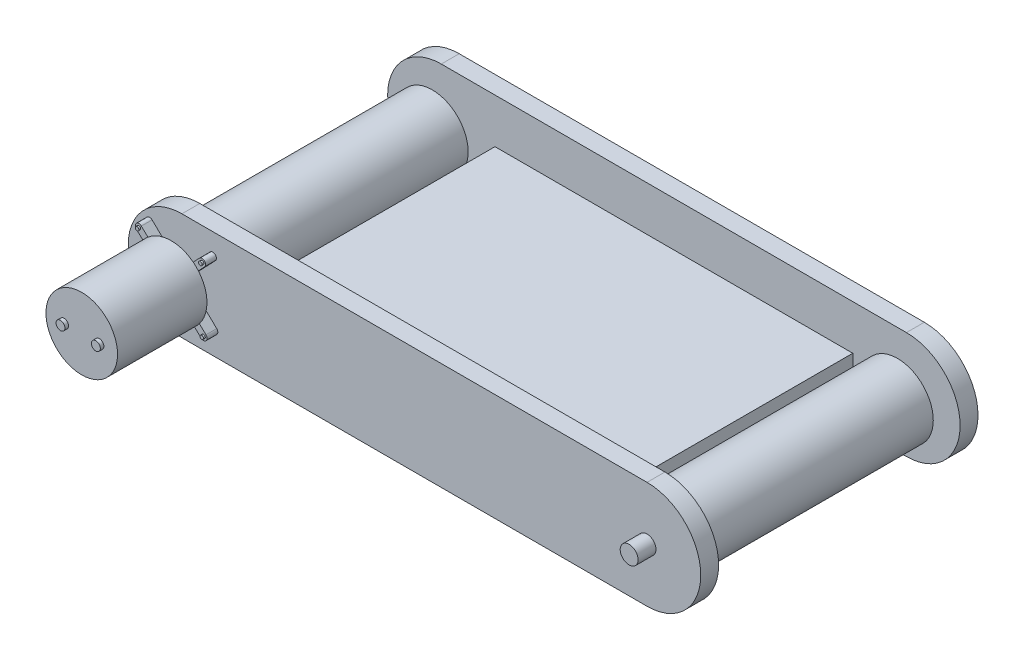
SolidWorks part; units mm, degrees
ref_plane "Front Plane" through (0, 0, 0) normal (0, 0, 1) x (1, 0, 0)
ref_plane "Top Plane" through (0, 0, 0) normal (0, 1, 0) x (1, 0, 0)
ref_plane "Right Plane" through (0, 0, 0) normal (1, 0, 0) x (0, 0, -1)
sketch "Sketch2" plane through (0, 0, 0) normal (0, 0, 1) x (1, 0, 0)
  line L0 (-130, 0) -> (130, 0) construction
  circle A0 centre (-130, 0) radius 20
  circle A1 centre (130, 0) radius 20
  dimension "D1" = 40
  dimension "D2" = 260
extrude "Boss-Extrude1" add sketch "Sketch2" along normal blind 62.5 and the other way blind 62.5
sketch "Sketch4" plane through (0, 0, 62.5) normal (0, 0, 1) x (1, 0, 0)
  circle A0 centre (-130, 0) radius 5
  circle A2 centre (-130, 0) radius 20 construction
  dimension "D1" = 10
extrude "Boss-Extrude5" add sketch "Sketch4" along normal blind 5
mirror "Mirror2" about plane through (0, 0, 0) normal (0, 0, 1) of "Boss-Extrude5"
sketch "Sketch9" plane through (0, 0, 62.5) normal (0, 0, 1) x (1, 0, 0)
  circle A0 centre (130, 0) radius 5
  circle A1 centre (130, 0) radius 20 construction
  dimension "D1" = 10
extrude "Boss-Extrude6" add sketch "Sketch9" along normal blind 25
mirror "Mirror4" about plane through (0, 0, 0) normal (0, 0, 1) of "Boss-Extrude6"
sketch "Sketch11" plane through (0, 0, 67.5) normal (0, 0, 1) x (1, 0, 0)
  line L0 (-130, 30) -> (130, 30)
  line L1 (68.75, 0) -> (-68.75, 0) construction
  line L2 (-130, -30) -> (130, -30)
  circle A0 centre (-130, 0) radius 30
  circle A1 centre (130, 0) radius 30
  circle A2 centre (-130, 0) radius 20 construction
  circle A3 centre (130, 0) radius 20 construction
  dimension "D1" = 60
extrude "Boss-Extrude8" add sketch "Sketch11" along normal blind 10 contours A1 L0 A0 L2 | A1 L0 | A0 region at (0, 0, 67.5) region at (130, 0, 67.5)
mirror "Mirror5" about plane through (0, 0, 0) normal (0, 0, 1) of "Boss-Extrude8"
sketch "Sketch12" plane through (0, 0, -67.5) normal (0, 0, 1) x (1, 0, 0)
  line L0 (0, 30) -> (0, -30) construction
  line L1 (-100, -5) -> (100, -5)
  line L2 (-100, -5) -> (-100, 5)
  line L3 (-100, 5) -> (100, 5)
  line L4 (100, -5) -> (100, 5)
  line L5 (-100, -5) -> (100, 5) construction
  line L6 (-100, 5) -> (100, -5) construction
  line L7 (-130, 30) -> (130, 30) construction
  line L8 (-130, -30) -> (130, -30) construction
  point P0 (0, 0)
  dimension "D1" = 10
  dimension "D2" = 200
extrude "Boss-Extrude9" add sketch "Sketch12" along normal up to surface (135 mm away) up to face at (135, 0, 67.5)
sketch "Sketch15" plane through (0, 0, 77.5) normal (0, 0, 1) x (1, 0, 0)
  circle A0 centre (-130, 0) radius 5
  arc A1 (-130, 30) -> (-130, -30) centre (-130, 0) ccw construction
  dimension "D1" = 10
extrude "Boss-Extrude10" add sketch "Sketch15" along normal blind 6
sketch "Sketch16" plane through (0, 0, 83.5) normal (0, 0, 1) x (1, 0, 0)
  circle A0 centre (-130, 0) radius 20
  circle A1 centre (-130, 0) radius 5 construction
  dimension "D1" = 40
extrude "Boss-Extrude11" add sketch "Sketch16" along normal blind 50
mirror "Mirror6" about plane through (0, 0, 0) normal (1, 0, 0) of "Mirror4"
sketch "Sketch17" plane through (0, 0, 133.5) normal (0, 0, 1) x (1, 0, 0)
  line L0 (-150, 0) -> (-142.389, 0) construction
  line L1 (-117.611, 0) -> (-110, 0) construction
  line L2 (-129.6073, 19.9961) -> (-129.6073, -19.9961) construction
  circle A0 centre (-139.889, 0) radius 2.5
  circle A1 centre (-120.111, 0) radius 2.5
  circle A3 centre (-130, 0) radius 20 construction
  point P13 (-129.6073, 0)
  dimension "D1" = 5
extrude "Boss-Extrude12" add sketch "Sketch17" along normal blind 2
sketch "Sketch18" plane through (0, 0, 77.5) normal (0, 0, 1) x (1, 0, 0)
  line L0 (-148.0704, 17.276) -> (-111.9296, -17.276) construction
  line L1 (-112.724, 18.0704) -> (-147.276, -18.0704) construction
  line L2 (-146.6883, 18.7217) -> (-110.5475, -15.8304)
  line L3 (-149.4525, 15.8304) -> (-113.3117, -18.7217)
  line L4 (-111.2783, 16.6883) -> (-145.8304, -19.4525)
  line L5 (-114.1696, 19.4525) -> (-148.7217, -16.6883)
  circle A0 centre (-148.0704, 17.276) radius 2
  circle A1 centre (-111.9296, -17.276) radius 2
  circle A2 centre (-112.724, 18.0704) radius 2
  circle A3 centre (-147.276, -18.0704) radius 2
  circle A6 centre (-130, 0) radius 5 construction
  circle A7 centre (-130, 0) radius 7.5
  point P12 (-130, 0)
  circle M7 centre (-130, 0) radius 5
  dimension "D2" = 4
  dimension "D4" = 15
  dimension "D1" = 90
  dimension "D3" = 50
extrude "Boss-Extrude13" add sketch "Sketch18" along normal up to surface (6 mm away) contours A0 | A0 L3 L2 M7 | A3 | A3 L4 L5 M7 | A1 | A1 L2 L3 M7 | A2 L5 L4 M7 | A2 | A7 region at (-141.1499, 10.6598, 77.5) region at (-148.0704, 17.276, 77.5) region at (-119.3402, 11.1499, 77.5) region at (-112.724, 18.0704, 77.5) region at (-140.6598, -11.1499, 77.5) region at (-147.276, -18.0704, 77.5) region at (-118.8501, -10.6598, 77.5) region at (-111.9296, -17.276, 77.5) up to face at (-125, 0, 83.5)
sketch "Sketch20" plane through (0, 0, 83.5) normal (0, 0, 1) x (1, 0, 0)
  circle A0 centre (-148.0704, 17.276) radius 1
  circle A1 centre (-112.724, 18.0704) radius 1
  circle A2 centre (-147.276, -18.0704) radius 1
  circle A3 centre (-111.9296, -17.276) radius 1
  arc A4 (-146.6883, 18.7217) -> (-149.4525, 15.8304) centre (-148.0704, 17.276) ccw construction
  arc A6 (-111.2783, 16.6883) -> (-114.1696, 19.4525) centre (-112.724, 18.0704) ccw construction
  arc A7 (-113.3117, -18.7217) -> (-110.5475, -15.8304) centre (-111.9296, -17.276) ccw construction
  arc A8 (-148.7217, -16.6883) -> (-145.8304, -19.4525) centre (-147.276, -18.0704) ccw construction
  dimension "D1" = 2
extrude "Boss-Extrude15" add sketch "Sketch20" along normal blind 1
